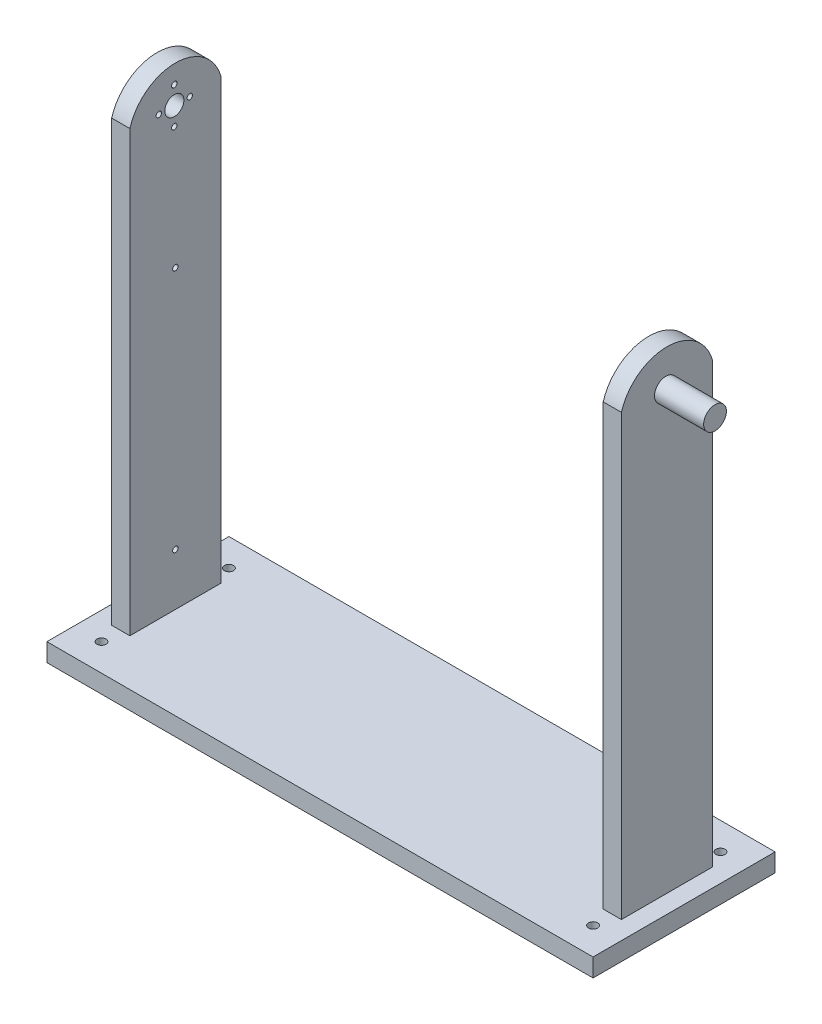
SolidWorks part; units mm, degrees
ref_plane "Front Plane" through (0, 0, 0) normal (0, 0, 1) x (1, 0, 0)
ref_plane "Top Plane" through (0, 0, 0) normal (0, 1, 0) x (1, 0, 0)
ref_plane "Right Plane" through (0, 0, 0) normal (1, 0, 0) x (0, 0, -1)
sketch "Sketch1" plane through (0, 0, 0) normal (0, 1, 0) x (1, 0, 0)
  line L0 (37.6647, -9.1264) -> (37.6647, -109.1264) construction
  line L1 (-112.3353, -109.1264) -> (187.6647, -109.1264)
  line L2 (-112.3353, -109.1264) -> (-112.3353, -9.1264)
  line L3 (-112.3353, -9.1264) -> (187.6647, -9.1264)
  line L4 (187.6647, -109.1264) -> (187.6647, -9.1264)
  line L5 (-112.3353, -109.1264) -> (187.6647, -9.1264) construction
  line L6 (-112.3353, -9.1264) -> (187.6647, -109.1264) construction
  line L7 (-112.3353, -59.1264) -> (187.6647, -59.1264) construction
  circle A0 centre (-97.3353, -24.1264) radius 2.5
  circle A1 centre (-97.3353, -94.1264) radius 2.5
  circle A2 centre (172.6647, -24.1264) radius 2.5
  circle A3 centre (172.6647, -94.1264) radius 2.5
  point P0 (37.6647, -59.1264)
  point P11 (0, 0)
  point P12 (0, 0)
  point P13 (-91.2127, -20.3672)
  dimension "D3" = 5
  dimension "D1" = 300
  dimension "D2" = 100
  dimension "D4" = 135
  dimension "D5" = 35
extrude "Boss-Extrude1" add sketch "Sketch1" along normal blind 10
sketch "Sketch2" plane through (0, 10, 0) normal (0, 1, 0) x (1, 0, 0)
  line L1 (37.6647, -9.1264) -> (37.6647, -124.3993)
  line L3 (177.6647, -33.5468) -> (167.6647, -33.5468)
  line L4 (-102.3353, -83.5468) -> (-92.3353, -83.5468)
  line L5 (-102.3353, -83.5468) -> (-102.3353, -33.5468)
  line L6 (-102.3353, -33.5468) -> (-92.3353, -33.5468)
  line L7 (-92.3353, -83.5468) -> (-92.3353, -33.5468)
  line L8 (-102.3353, -83.5468) -> (-92.3353, -33.5468) construction
  line L9 (-102.3353, -33.5468) -> (-92.3353, -83.5468) construction
  line L10 (167.6647, -83.5468) -> (167.6647, -33.5468)
  line L11 (177.6647, -83.5468) -> (167.6647, -83.5468)
  line L12 (177.6647, -83.5468) -> (177.6647, -33.5468)
  dimension "D1" = 50
  dimension "D2" = 10
extrude "Boss-Extrude2" add sketch "Sketch2" along normal blind 260 contours L5 L4 L7 L6 | L3 L10 L11 L12
ref_plane "Plane1" through (-82.3353, 0, 0) normal (-1, 0, 0) x (0, 0, 1)
sketch "Sketch3" plane through (-82.3353, 0, 0) normal (-1, 0, 0) x (0, 0, 1)
  line L0 (83.5468, 270) -> (33.5468, 270) construction
  circle A0 centre (59.1264, 250) radius 5.25
  point P2 (0, 0)
  dimension "D1" = 10.5
extrude "Cut-Extrude1" cut sketch "Sketch3" along normal up to surface (20 mm away) up to face at (-102.3353, 140, 58.5468)
sketch "Sketch4" plane through (-102.3353, 0, 0) normal (-1, 0, 0) x (0, 0, 1)
  line L0 (33.5468, 270) -> (33.5468, 10) construction
  line L1 (83.5468, 270) -> (83.5468, 10) construction
  line L2 (33.5468, 251.2727) -> (33.5468, 270)
  line L3 (33.5468, 270) -> (83.5468, 270)
  line L4 (83.5468, 270) -> (83.5468, 251.2727)
  arc A0 (33.5468, 251.2727) -> (83.5468, 251.2727) centre (58.5468, 243.9495) cw
  point P3 (83.5468, 251.2727)
  line M3 (83.5468, 10) -> (83.5468, 270)
  line M4 (83.5468, 270) -> (33.5468, 270)
  line M5 (33.5468, 270) -> (33.5468, 10)
extrude "Cut-Extrude2" cut sketch "Sketch4" against normal through all and the other way through all contours A0 M4 M3 | A0 L3 M5 region at (-102.3353, 265.0498, 77.8212) region at (-102.3353, 265.0498, 39.2724)
sketch "Sketch5" plane through (-102.3353, 0, 0) normal (-1, 0, 0) x (0, 0, 1)
  line L0 (83.5468, 251.2727) -> (83.5468, 10) construction
  circle A0 centre (58.5468, 172.5641) radius 1.5
  circle A3 centre (58.5468, 38.5641) radius 1.5
  dimension "D1" = 3
  dimension "D3" = 25
  dimension "D2" = 2
extrude "Cut-Extrude3" cut sketch "Sketch5" against normal up to surface (10 mm away) up to face at (-92.3353, 250, 64.3764)
sketch "Sketch7" plane through (-102.3353, 0, 0) normal (-1, 0, 0) x (0, 0, 1)
  line L0 (59.1264, 255.25) -> (59.1264, 244.75) construction
  line L1 (53.8764, 250) -> (64.3764, 250) construction
  circle A0 centre (59.1264, 250) radius 5.25 construction
  circle A1 centre (59.1264, 260) radius 1.5
  circle A2 centre (59.1264, 240) radius 1.5
  point P12 (59.1264, 250)
  dimension "D1" = 3
  dimension "D2" = 10
  dimension "D3" = 20
extrude "Cut-Extrude6" cut sketch "Sketch7" against normal up to surface (10 mm away) up to face at (-92.3353, 172.5641, 60.0468)
sketch "Sketch8" plane through (-102.3353, 0, 0) normal (-1, 0, 0) x (0, 0, 1)
  line L0 (59.1264, 255.25) -> (59.1264, 244.75) construction
  line L1 (53.8764, 250) -> (64.3764, 250) construction
  circle A0 centre (59.1264, 250) radius 5.25 construction
  circle A1 centre (50.6264, 250) radius 1.5
  circle A2 centre (67.6264, 250) radius 1.5
  point P9 (59.1264, 250)
  dimension "D1" = 3
  dimension "D2" = 8.5
extrude "Cut-Extrude7" cut sketch "Sketch8" against normal up to surface (10 mm away) up to face at (-92.3353, 260, 60.6264)
sketch "Sketch12" plane through (177.6647, 0, 0) normal (1, 0, 0) x (0, 0, -1)
  circle A1 centre (-59.1264, 250) radius 6.25
  dimension "D2" = 12.5
extrude "Boss-Extrude4" add sketch "Sketch12" along normal blind 27
sketch "Sketch13" plane through (167.6647, 0, 0) normal (-1, 0, 0) x (0, 0, 1)
  line L0 (59.1264, 250) -> (67.6264, 250) construction
  circle A0 centre (59.1264, 250) radius 5.25
  dimension "D1" = 10.5
extrude "Cut-Extrude10" cut sketch "Sketch13" against normal blind 34
